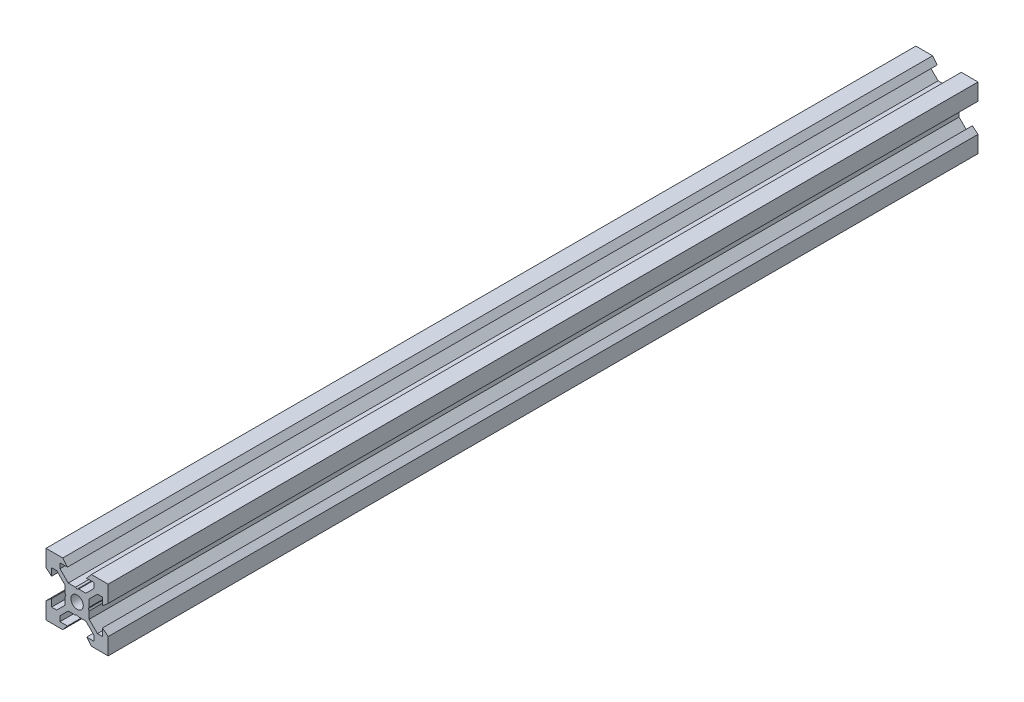
SolidWorks part; units mm, degrees
ref_plane "Front Plane" through (0, 0, 0) normal (0, 0, 1) x (1, 0, 0)
ref_plane "Top Plane" through (0, 0, 0) normal (0, 1, 0) x (1, 0, 0)
ref_plane "Right Plane" through (0, 0, 0) normal (1, 0, 0) x (0, 0, -1)
sketch "Sketch1" plane through (0, 0, 0) normal (0, 0, 1) x (1, 0, 0)
  line L0 (10, 10) -> (4.6104, 10) construction
  line L1 (10, 10) -> (10, 4.6104) construction
  line L2 (10, -10) -> (10, -4.6104) construction
  line L3 (10, -10) -> (4.6104, -10) construction
  line L4 (10, 10) -> (10, 4.6104)
  line L5 (6.5607, 5.5) -> (8.2, 5.5)
  line L6 (5.5, 8.2) -> (5.5, 6.5607)
  line L7 (10, 10) -> (4.6104, 10)
  line L8 (10, 10) -> (10, 4.6104)
  line L9 (6.5607, 5.5) -> (3.9, 2.8393)
  line L10 (5.5, 6.5607) -> (2.8393, 3.9)
  line L11 (10, 4.6104) -> (8.2, 3.1)
  line L12 (4.6104, 10) -> (3.1, 8.2)
  line L13 (8.2, 3.1) -> (8.2, 5.5)
  line L14 (3.1, 8.2) -> (5.5, 8.2)
  line L15 (-6.5607, 5.5) -> (-8.2, 5.5)
  line L16 (6.5607, -5.5) -> (8.2, -5.5)
  line L17 (3.1, -8.2) -> (5.5, -8.2)
  line L18 (8.2, -3.1) -> (8.2, -5.5)
  line L19 (4.6104, -10) -> (3.1, -8.2)
  line L20 (10, -4.6104) -> (8.2, -3.1)
  line L21 (0.5196, -3.9) -> (0, -3.6)
  line L22 (0.5196, 3.9) -> (0, 3.6)
  line L23 (3.6, 0) -> (3.9, -0.5196)
  line L24 (3.9, 0.5196) -> (3.6, 0)
  line L25 (3.9, 0.5196) -> (3.9, 2.8393)
  line L26 (2.8393, 3.9) -> (0.5196, 3.9)
  line L27 (3.9, -2.8393) -> (3.9, -0.5196)
  line L28 (2.8393, -3.9) -> (0.5196, -3.9)
  line L29 (5.5, -6.5607) -> (2.8393, -3.9)
  line L30 (6.5607, -5.5) -> (3.9, -2.8393)
  line L31 (10, -10) -> (10, -4.6104)
  line L32 (10, -10) -> (4.6104, -10)
  line L33 (5.5, -8.2) -> (5.5, -6.5607)
  line L34 (-6.5607, -5.5) -> (-8.2, -5.5)
  line L35 (10, -10) -> (10, -4.6104)
  line L36 (0, 0) -> (0, 8.2) construction
  line L37 (-10, -10) -> (-4.6104, -10) construction
  line L38 (-10, -10) -> (-10, -4.6104) construction
  line L39 (-10, 10) -> (-10, 4.6104) construction
  line L40 (-10, 10) -> (-4.6104, 10) construction
  line L41 (-10, -10) -> (-10, -4.6104)
  line L43 (-5.5, -8.2) -> (-5.5, -6.5607)
  line L44 (-10, -10) -> (-4.6104, -10)
  line L45 (-10, -10) -> (-10, -4.6104)
  line L46 (-6.5607, -5.5) -> (-3.9, -2.8393)
  line L47 (-5.5, -6.5607) -> (-2.8393, -3.9)
  line L48 (-2.8393, -3.9) -> (-0.5196, -3.9)
  line L49 (-3.9, -2.8393) -> (-3.9, -0.5196)
  line L50 (-2.8393, 3.9) -> (-0.5196, 3.9)
  line L51 (-3.9, 0.5196) -> (-3.9, 2.8393)
  line L52 (-3.9, 0.5196) -> (-3.6, 0)
  line L53 (-3.6, 0) -> (-3.9, -0.5196)
  line L54 (-0.5196, 3.9) -> (0, 3.6)
  line L55 (-0.5196, -3.9) -> (0, -3.6)
  line L56 (-10, -4.6104) -> (-8.2, -3.1)
  line L57 (-4.6104, -10) -> (-3.1, -8.2)
  line L58 (-8.2, -3.1) -> (-8.2, -5.5)
  line L59 (-3.1, -8.2) -> (-5.5, -8.2)
  line L60 (-10, -10) -> (10, -10) construction
  line L61 (-10, -10) -> (-10, 10) construction
  line L62 (-3.1, 8.2) -> (-5.5, 8.2)
  line L63 (-8.2, 3.1) -> (-8.2, 5.5)
  line L64 (-4.6104, 10) -> (-3.1, 8.2)
  line L65 (-10, 4.6104) -> (-8.2, 3.1)
  line L66 (-5.5, 6.5607) -> (-2.8393, 3.9)
  line L67 (-6.5607, 5.5) -> (-3.9, 2.8393)
  line L68 (-10, 10) -> (-10, 4.6104)
  line L69 (-10, 10) -> (-4.6104, 10)
  line L70 (-5.5, 8.2) -> (-5.5, 6.5607)
  line L71 (-10, 10) -> (10, 10) construction
  line L72 (-10, 10) -> (-10, 4.6104)
  line L73 (10, -10) -> (10, 10) construction
  line L74 (-10, -10) -> (10, 10) construction
  line L75 (-10, 10) -> (10, -10) construction
  circle A0 centre (0, 0) radius 2
  dimension "D7" = 4
  dimension "D1" = 20
  dimension "D2" = 5.3896
  dimension "D3" = 4.5
  dimension "D4" = 50
  dimension "D5" = 1.8
  dimension "D6" = 1.5104
  dimension "D8" = 5.5
  dimension "D9" = 120
  dimension "D10" = 0.3
  dimension "D11" = 2.3197
  dimension "D12" = 7.8
  dimension "D13" = 7.8
  dimension "D14" = 1.5
  dimension "D15" = 2.6607
extrude "Boss-Extrude1" add sketch "Sketch1" along normal mid plane 280 contours L70 L62 L64 L69 L68 L65 L63 L15 L67 L51 L52 L53 L49 L46 L34 L58 L56 L41 L44 L57 L59 L43 L47 L48 L55 L21 L28 L29 L33 L17 L19 L32 L31 L20 L18 L16 L30 L27 L23 L24 L25 L9 L5 L13 L11 L4 L7 L12 L14 L6 L10 region at (9.7172, 7.3052, 0)
